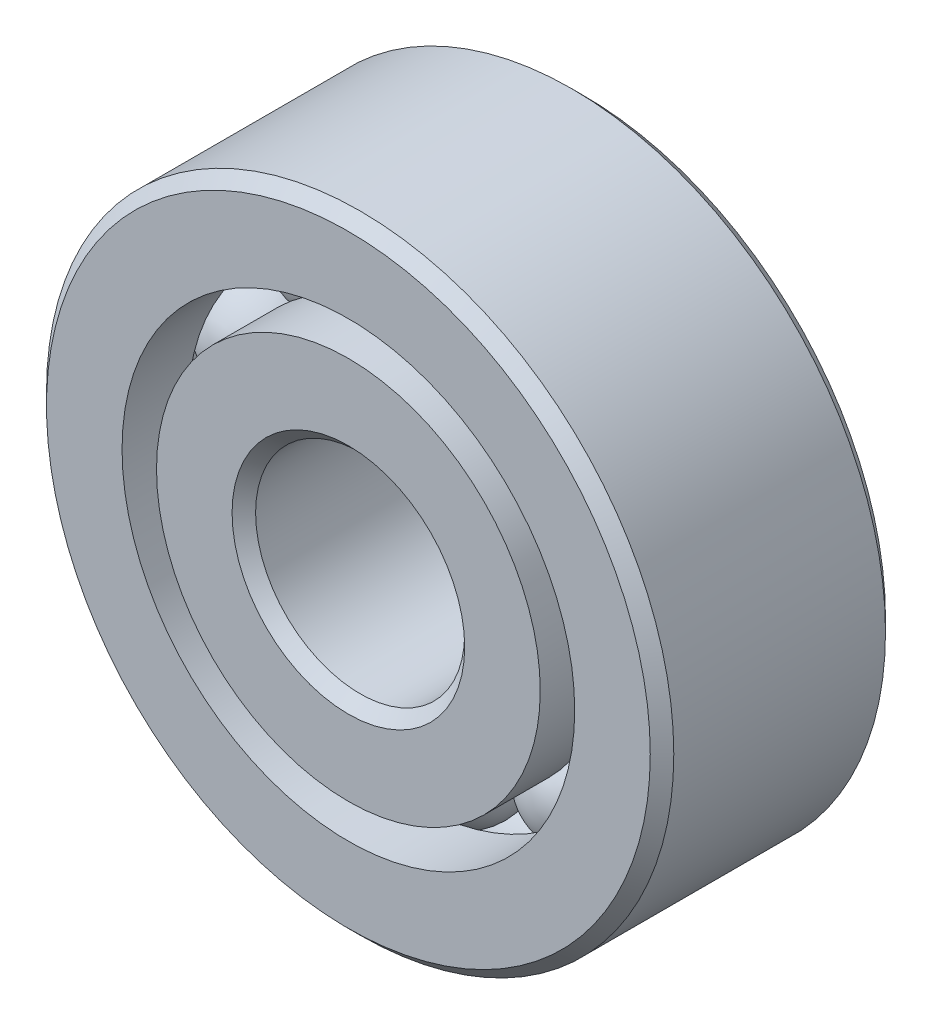
SolidWorks part; units mm, degrees
ref_plane "Front Plane" through (0, 0, 0) normal (0, 0, 1) x (1, 0, 0)
ref_plane "Top Plane" through (0, 0, 0) normal (0, 1, 0) x (1, 0, 0)
ref_plane "Right Plane" through (0, 0, 0) normal (1, 0, 0) x (0, 0, -1)
sketch "Sketch1" plane through (0, 0, 0) normal (1, 0, 0) x (0, 0, -1)
  line L0 (-3.5719, 0) -> (3.5719, 0) construction
  line L1 (0, 9.525) -> (0, -9.525) construction
  line L2 (3.2147, 9.525) -> (-3.2147, 9.525)
  line L3 (-3.2147, 9.525) -> (-3.5719, 9.1678)
  line L4 (-3.5719, 9.1678) -> (-3.5719, 6.8734)
  line L5 (-3.5719, 6.8734) -> (-1.5875, 6.8734)
  line L6 (3.5719, 6.8734) -> (1.5875, 6.8734)
  line L7 (3.5719, 9.1678) -> (3.5719, 6.8734)
  line L8 (3.2147, 9.525) -> (3.5719, 9.1678)
  line L9 (0, 9.525) -> (0, 6.35) construction
  line L10 (0, 6.35) -> (0, 3.175) construction
  arc A0 (-1.5875, 6.8734) -> (1.5875, 6.8734) centre (0, 6.35) cw
  point P14 (0, 3.175)
  dimension "D3" = 3.175
  dimension "D1" = 45
  dimension "Width" = 7.1437
  dimension "OD" = 19.05
  dimension "D2" = 0.3572
  dimension "Shaft Dia" = 6.35
  dimension "D4" = 0.5234
revolve "Revolve1" add sketch "Sketch1" angle 360 about L0
sketch "Sketch3" plane through (0, 0, 0) normal (1, 0, 0) x (0, 0, -1)
  line L0 (-3.5719, 5.8266) -> (-1.5875, 5.8266)
  line L1 (0, 9.525) -> (0, -9.525) construction
  line L2 (-3.5719, 9.1678) -> (-3.5719, 6.8734) construction
  line L3 (-3.5719, 5.8266) -> (-3.5719, 3.5322)
  line L4 (-3.2147, 9.525) -> (-3.5719, 9.1678) construction
  line L5 (-3.5719, 3.5322) -> (-3.2147, 3.175)
  line L6 (-3.2147, 3.175) -> (3.2147, 3.175)
  line L7 (3.2147, 9.525) -> (3.2147, -9.525) construction
  line L8 (3.2147, 3.175) -> (3.5719, 3.5322)
  line L9 (3.5719, -9.1678) -> (3.5719, 9.1678) construction
  line L10 (3.5719, 3.5322) -> (3.5719, 5.8266)
  line L11 (3.5719, 5.8266) -> (1.5875, 5.8266)
  line L13 (3.2147, 9.525) -> (3.5719, 9.1678) construction
  arc A0 (1.5875, 6.8734) -> (-1.5875, 6.8734) centre (0, 6.35) ccw construction
  arc A1 (1.5875, 5.8266) -> (-1.5875, 5.8266) centre (0, 6.35) cw
revolve "Revolve3" add sketch "Sketch3" angle 360 about L0
sketch "Sketch4" plane through (0, 0, 0) normal (1, 0, 0) x (0, 0, -1)
  line L0 (-1.6715, 6.35) -> (1.6715, 6.35)
  arc A2 (-1.6715, 6.35) -> (1.6715, 6.35) centre (0, 6.35) cw
  arc A3 (1.5875, 6.8734) -> (-1.5875, 6.8734) centre (0, 6.35) ccw construction
revolve "Revolve4" add sketch "Sketch4" angle 360 about L0
ref_axis "Axis1" through (0, 0, -3.5719) along (0, 0, 1)
pattern_circular "CirPattern1" count 10 every 36 about axis through (0, 0, -3.5719) along (0, 0, 1) of bodies 104
equation "\"D2@Sketch1\" = \"Width@Sketch1\"*.05"
equation "\"D3@Sketch1\" = \"Width@Sketch1\"/2.25"
equation "\"D4@Sketch1\" = (((\"OD@Sketch1\"-\"Width@Sketch1\")/2)/3.25)/3.5"
equation "\"D2@CirPattern1\" = 360/\"Balls@CirPattern1\""
